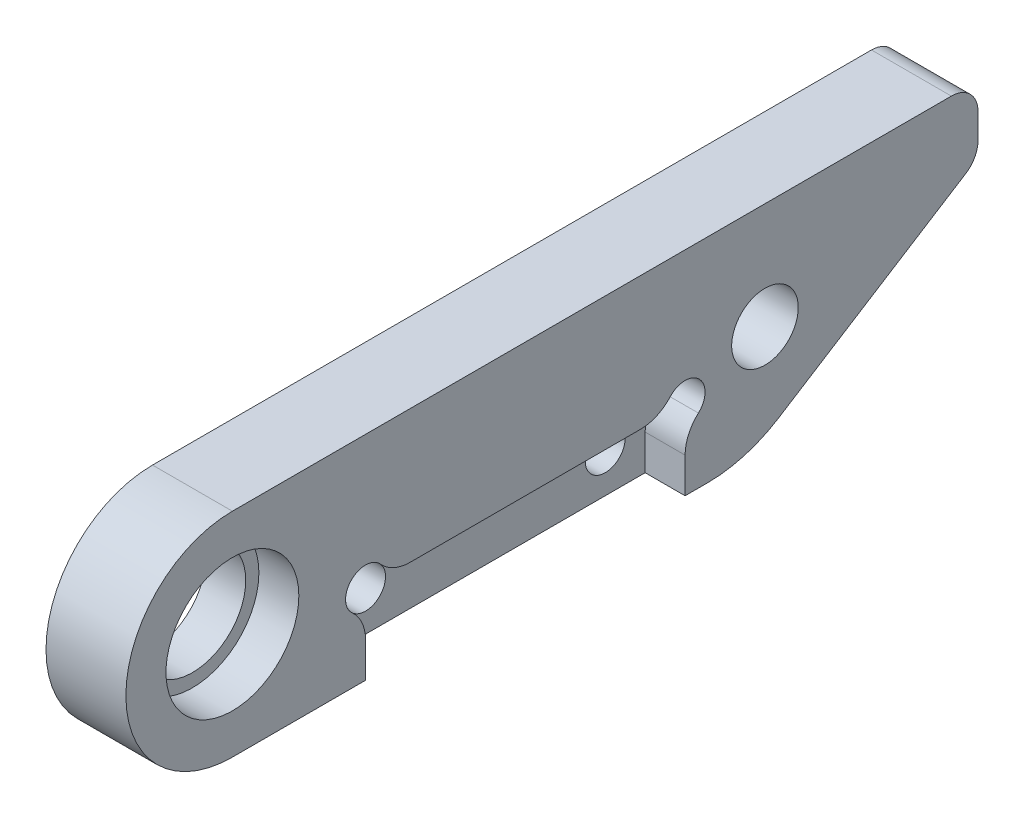
SolidWorks part; units mm, degrees
material "1060 Alloy"
ref_plane "Front Plane" through (0, 0, 0) normal (0, 0, 1) x (1, 0, 0)
ref_plane "Top Plane" through (0, 0, 0) normal (0, 1, 0) x (1, 0, 0)
ref_plane "Right Plane" through (0, 0, 0) normal (1, 0, 0) x (0, 0, -1)
sketch "Sketch27" plane through (0, 0, 0) normal (1, 0, 0) x (0, 0, -1)
  line L2 (10, 50) -> (66, 50)
  line L3 (10, 42) -> (31.9317, 42) construction
  line L4 (31.9317, 42) -> (31.9317, 54) construction
  line L6 (10, 34) -> (48.5644, 34)
  line L7 (31.9317, 54) -> (10, 42) construction
  line L8 (0, 0) -> (60, 0) construction
  line L9 (0, 0) -> (0, 58) construction
  line L10 (0, 58) -> (60, 58) construction
  line L11 (60, 0) -> (60, 58) construction
  line L12 (66, 50) -> (66, 45)
  line L13 (48.5644, 34) -> (66, 45)
  arc A0 (10, 50) -> (10, 34) centre (10, 42) ccw
  circle A1 centre (50, 42) radius 6 construction
  circle A3 centre (10, 42) radius 5.6 construction
  circle A5 centre (10, 42) radius 4
  circle A6 centre (50, 42) radius 2.5
  dimension "D9" = 12
  dimension "D10" = 5
  dimension "D12" = 8
  dimension "D13" = 8
  dimension "D14" = 5
  dimension "D6" = 16
  dimension "D16" = 11.2
  dimension "D1" = 60
  dimension "D2" = 58
  dimension "D3" = 42
  dimension "D4" = 10
  dimension "D5" = 50
  dimension "D7" = 42
  dimension "D8" = 12
  dimension "D17" = 25
extrude "Boss-Extrude1" add sketch "Sketch27" along normal blind 6
sketch "Sketch33" plane through (6, 0, 0) normal (1, 0, 0) x (0, 0, -1)
  circle A0 centre (10, 42) radius 4.99
  dimension "D1" = 9.98
extrude "Cut-Extrude2" cut sketch "Sketch33" against normal blind 3
sketch "Sketch34" plane through (6, 0, 0) normal (1, 0, 0) x (0, 0, -1)
  line L0 (20, 34) -> (44, 34)
  line L1 (20, 34) -> (20, 40)
  line L2 (44, 34) -> (44, 40)
  line L3 (20, 40) -> (44, 40)
  line L4 (10, 34) -> (48.5644, 34) construction
  circle A0 centre (50, 42) radius 2.5 construction
  dimension "D1" = 24
  dimension "D2" = 6
  dimension "D3" = 6
extrude "Cut-Extrude3" cut sketch "Sketch34" against normal blind 3
sketch "Sketch35" plane through (6, 0, 0) normal (1, 0, 0) x (0, 0, -1)
  circle A0 centre (20, 40) radius 1.5
  circle A1 centre (44, 40) radius 1.5
  dimension "D1" = 3
extrude "Cut-Extrude4" cut sketch "Sketch35" against normal up to surface (3 mm away) up to face at (3, 37, -32)
fillet "Fillet1" radius 3 4 edges at (4.5, 38.5, -44) (4.5, 40, -42.5) (4.5, 38.5, -20) (4.5, 40, -21.5)
sketch "Sketch36" plane through (3, 0, 0) normal (1, 0, 0) x (0, 0, -1)
  line L0 (20, 36.6459) -> (20, 34) construction
  line L1 (20, 34) -> (44, 34) construction
  line L2 (44, 34) -> (44, 36.6459) construction
  circle A0 centre (23, 37) radius 1.5
  circle A1 centre (41, 37) radius 1.5
  dimension "D1" = 3
  dimension "D2" = 3
  dimension "D3" = 3
  dimension "D4" = 3
  dimension "D5" = 3
extrude "Cut-Extrude5" cut sketch "Sketch36" against normal up to next
fillet "Fillet3" radius 2 2 edges at (3, 50, -66) (3, 45, -66)
fillet "Fillet4" radius 10 1 edges at (3, 34, -48.5644)
